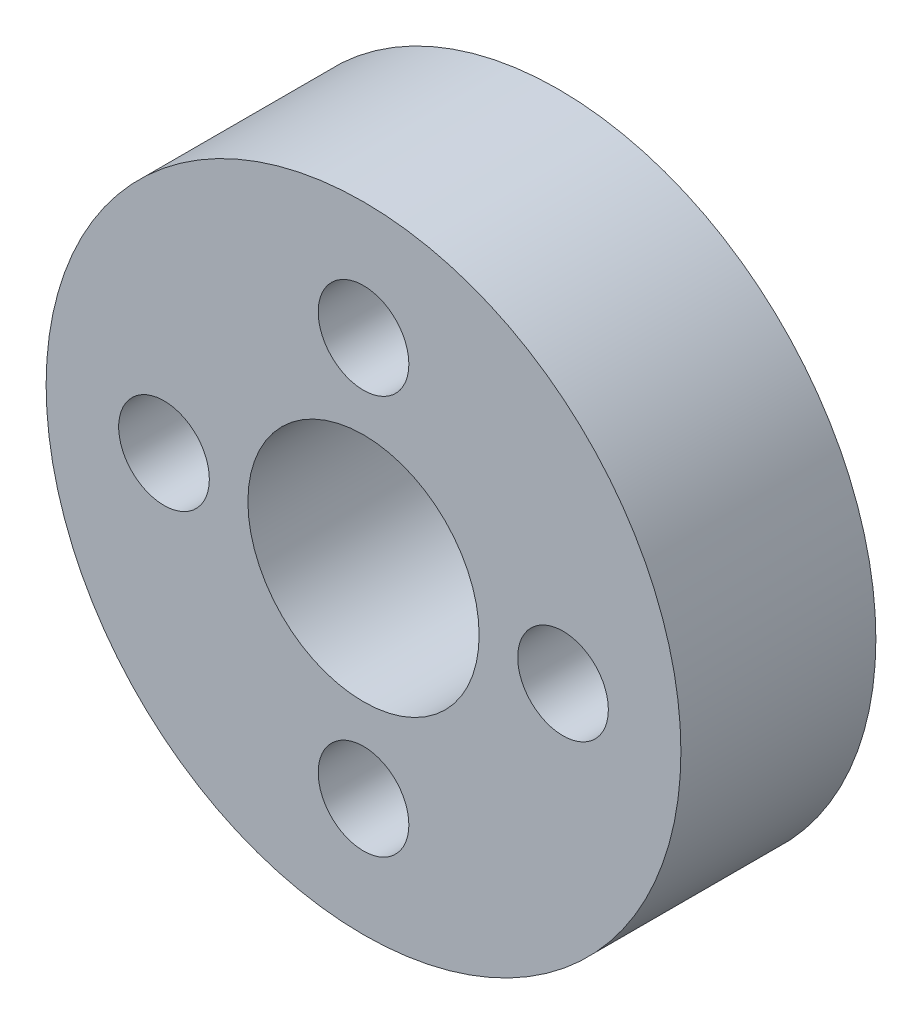
SolidWorks part; units mm, degrees
ref_plane "Front Plane" through (0, 0, 0) normal (0, 0, 1) x (1, 0, 0)
ref_plane "Top Plane" through (0, 0, 0) normal (0, 1, 0) x (1, 0, 0)
ref_plane "Right Plane" through (0, 0, 0) normal (1, 0, 0) x (0, 0, -1)
sketch "Sketch1" plane through (0, 0, 0) normal (0, 0, 1) x (1, 0, 0)
  line L0 (0, 11.176) -> (0, 0) construction
  line L5 (0, 0) -> (11.176, 0) construction
  line L6 (0, -11.176) -> (0, 0) construction
  line L7 (0, 0) -> (-11.176, 0) construction
  circle A0 centre (0, 0) radius 17.78
  circle A1 centre (-11.176, 0) radius 2.54
  circle A2 centre (0, -11.176) radius 2.54
  circle A3 centre (11.176, 0) radius 2.54
  circle A4 centre (0, 11.176) radius 2.54
  circle A5 centre (0, 0) radius 6.477
  dimension "D1" = 35.56
  dimension "D4" = 5.08
  dimension "D2" = 12.954
  dimension "D3" = 11.176
extrude "Boss-Extrude1" add sketch "Sketch1" along normal blind 10.922
sketch "Sketch2" plane through (0, 0, 0) normal (0, 0, -1) x (-1, 0, 0)
  line L1 (-8.255, -8.255) -> (8.255, -8.255)
  line L2 (-8.255, -8.255) -> (-8.255, 8.255)
  line L3 (-8.255, 8.255) -> (8.255, 8.255)
  line L4 (8.255, -8.255) -> (8.255, 8.255)
  line L5 (-8.255, -8.255) -> (8.255, 8.255) construction
  line L6 (-8.255, 8.255) -> (8.255, -8.255) construction
  circle A0 centre (0, 0) radius 6.477 construction
  circle A1 centre (0, 0) radius 6.477
  point P0 (0, 0)
  dimension "D1" = 16.51
extrude "Boss-Extrude2" add sketch "Sketch2" along normal blind 3.175
